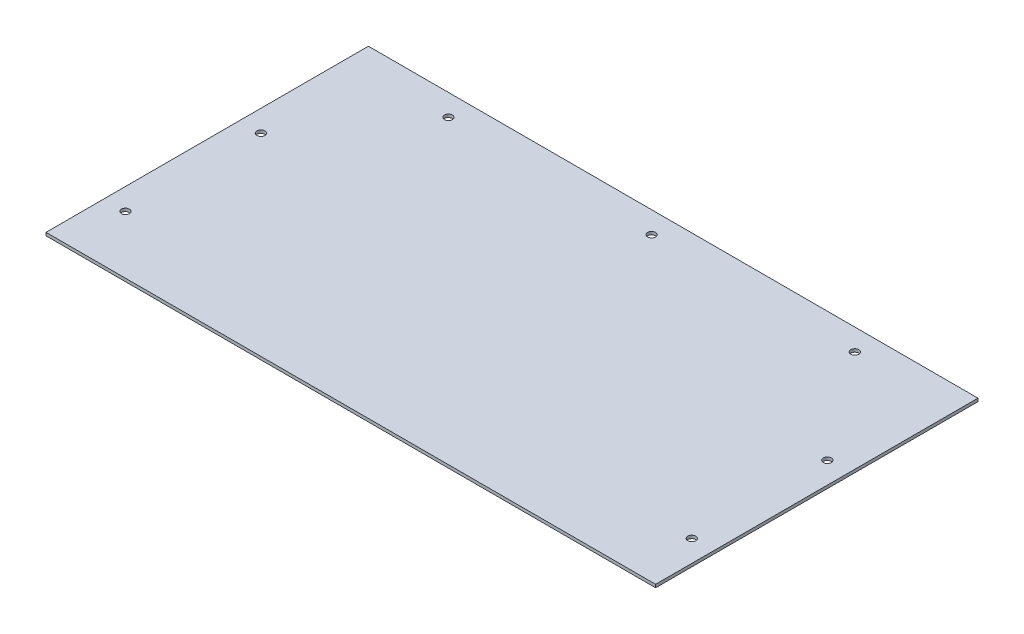
SolidWorks part; units mm, degrees
material "6061-T6 (SS)"
ref_plane "X-Y Datum" through (0, 0, 0) normal (0, 0, 1) x (1, 0, 0)
ref_plane "X-Z Datum" through (0, 0, 0) normal (0, 1, 0) x (1, 0, 0)
ref_plane "Y-Z Datum" through (0, 0, 0) normal (1, 0, 0) x (0, 0, -1)
sketch "Sketch1" plane through (0, 0, 0) normal (0, 0, 1) x (1, 0, 0)
  line L1 (-228.6, -1.143) -> (228.6, -1.143)
  line L2 (-228.6, -1.143) -> (-228.6, 1.143)
  line L3 (-228.6, 1.143) -> (228.6, 1.143)
  line L4 (228.6, -1.143) -> (228.6, 1.143)
  line L5 (-228.6, -1.143) -> (228.6, 1.143) construction
  line L6 (-228.6, 1.143) -> (228.6, -1.143) construction
  point P0 (0, 0)
  dimension "D1" = 2.286
  dimension "D2" = 457.2
extrude "Boss-Extrude1" add sketch "Sketch1" along normal blind 238.62
sketch "Sketch2" plane through (0, 0, 0) normal (0, 0, -1) x (-1, 0, 0)
  line L22 (-228.6, 1.143) -> (-228.6, -1.143)
  line L23 (-228.6, -1.143) -> (228.6, -1.143)
  line L24 (228.6, -1.143) -> (228.6, 1.143)
  line L25 (228.6, 1.143) -> (-228.6, 1.143)
  line L26 (-228.6, 1.143) -> (-228.6, -1.143)
  line L27 (-228.6, -1.143) -> (228.6, -1.143)
  line L28 (228.6, -1.143) -> (228.6, 1.143)
  line L29 (228.6, 1.143) -> (-228.6, 1.143)
  line M6 (-228.6, -1.143) -> (228.6, -1.143)
  line M8 (228.6, 1.143) -> (-228.6, 1.143)
  dimension "D1" = 0
extrude "Boss-Extrude2" add sketch "Sketch2" along normal blind 3.175 contours M8 M6 | M8 M6 region at (0, 0, 0)
sketch "Sketch6" plane through (0, -1.143, 0) normal (0, -1, 0) x (1, 0, 0)
  circle A0 centre (-212.419, 195.2448) radius 3 construction
  circle A1 centre (212.419, 195.2448) radius 3 construction
  circle A2 centre (212.419, 93.6448) radius 3 construction
  circle A3 centre (152.4, 13.0175) radius 3 construction
  circle A4 centre (0, 13.0175) radius 3 construction
  circle A5 centre (-152.4, 13.0175) radius 3 construction
  circle A6 centre (-212.419, 93.6448) radius 3 construction
  circle A7 centre (-212.419, 195.2448) radius 3
  circle A8 centre (212.419, 195.2448) radius 3
  circle A9 centre (212.419, 93.6448) radius 3
  circle A10 centre (152.4, 13.0175) radius 3
  circle A11 centre (0, 13.0175) radius 3
  circle A12 centre (-152.4, 13.0175) radius 3
  circle A13 centre (-212.419, 93.6448) radius 3
extrude "Cut-Extrude6" cut sketch "Sketch6" against normal blind 2.286
